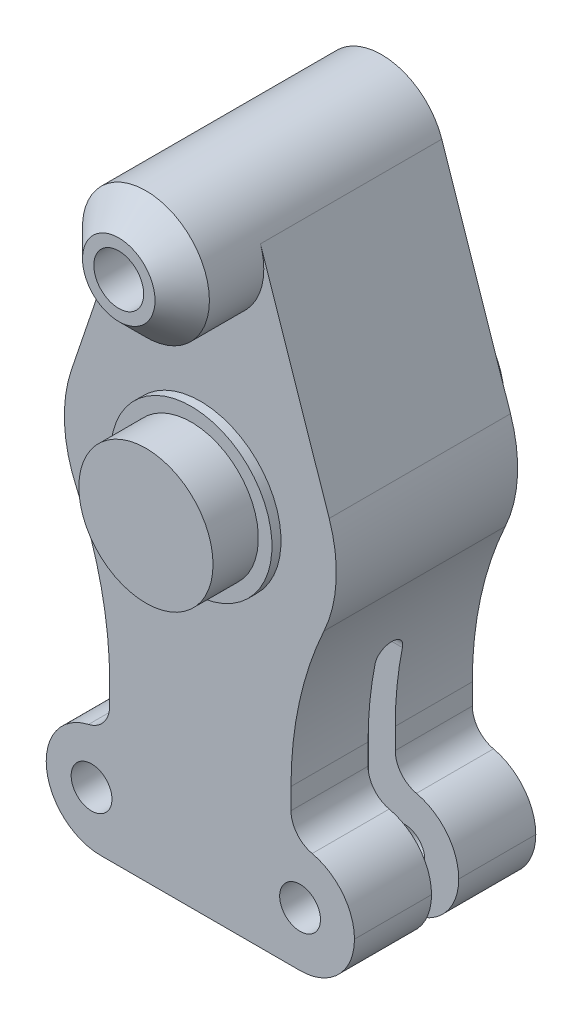
SolidWorks part; units mm, degrees
ref_plane "Спереди" through (0, 0, 0) normal (0, 0, 1) x (1, 0, 0)
ref_plane "Сверху" through (0, 0, 0) normal (0, 1, 0) x (1, 0, 0)
ref_plane "Справа" through (0, 0, 0) normal (1, 0, 0) x (0, 0, -1)
sketch "Эскиз1" plane through (0, 0, 0) normal (0, 0, 1) x (1, 0, 0)
  circle A0 centre (0, 0) radius 7.5 construction
  circle A1 centre (0, 0) radius 7.4
  dimension "D1" = 15
  dimension "measurement_tolerance" = 0.1
extrude "Бобышка-Вытянуть1" add sketch "Эскиз1" along normal blind 5
sketch "Эскиз2" plane through (0, 0, 0) normal (0, 0, -1) x (-1, 0, 0)
  circle A2 centre (0, 0) radius 8.9
  circle A3 centre (0, 0) radius 8.9
  dimension "D1" = 1.5
extrude "Бобышка-Вытянуть2" add sketch "Эскиз2" along normal blind 1
sketch "Эскиз3" plane through (0, 0, -1) normal (0, 0, -1) x (-1, 0, 0)
  circle A0 centre (0, 0) radius 15
  dimension "D3" = 30
extrude "Бобышка-Вытянуть3" add sketch "Эскиз3" along normal blind 20
sketch "Эскиз11" plane through (0, 0, 0) normal (0, 1, 0) x (1, 0, 0)
  line L1 (-10, 1) -> (10, 1)
  line L2 (0, 21) -> (0, 1) construction
  line L3 (15, 21) -> (-15, 21) construction
  line L4 (-8.9, 1) -> (8.9, 1) construction
  line L5 (-10, 1) -> (-10, 21)
  line L6 (-10, 21) -> (10, 21)
  line L7 (10, 1) -> (10, 21)
  line L8 (-10, 1) -> (10, 21) construction
  line L9 (-10, 21) -> (10, 1) construction
  point P0 (0, 11)
  dimension "D2" = 20
extrude "Бобышка-Вытянуть8" add sketch "Эскиз11" against normal blind 40
sketch "Эскиз4" plane through (0, 0, -1) normal (0, 0, -1) x (-1, 0, 0)
  line L0 (0, 0) -> (0, 25) construction
  line L1 (-6.6319, 27.24) -> (-14.2113, 4.8)
  line L2 (-14.2113, 4.8) -> (14.2113, 4.8)
  line L4 (14.2113, 4.8) -> (6.6319, 27.24)
  arc A0 (6.6319, 27.24) -> (-6.6319, 27.24) centre (0, 25) ccw
  circle A1 centre (0, 0) radius 15 construction
  dimension "D1" = 14
  dimension "D2" = 25
extrude "Бобышка-Вытянуть4" add sketch "Эскиз4" along normal up to surface (20 mm away)
sketch "Эскиз5" plane through (0, 0, -1) normal (0, 0, 1) x (1, 0, 0)
  circle A0 centre (0, 25) radius 7
  arc A1 (6.6319, 27.24) -> (-6.6319, 27.24) centre (0, 25) ccw construction
  dimension "D1" = 14
extrude "Бобышка-Вытянуть5" add sketch "Эскиз5" along normal blind 9
hole_wizard "Цековка для винта с внутренним шестигранником M51" positions "Эскиз7" profile "Эскиз6" counterbore size "M5" standard "Ansi Metric" end condition through all
sketch "Эскиз7" plane through (0.4817, 0.6241, -21) normal (0, 0, -1) x (-1, 0, 0)
  circle A0 centre (0.4817, 24.3759) radius 7 construction
  point P1 (0.4817, 24.3759)
sketch "Эскиз6" plane through (0, 25, -21) normal (1, 0, 0) x (0, 1, 0)
  line L0 (0, 0) -> (0, 29)
  line L1 (0, 29) -> (2.75, 29)
  line L3 (2.75, 29) -> (2.75, 14)
  line L4 (2.75, 14) -> (5.25, 14)
  line L5 (5.25, 14) -> (5.25, 0)
  line L7 (5.25, 0) -> (0, 0)
  line L11 (0, -6.35) -> (0, 107.95) construction
  dimension "Диаметр сквозного отверстия" = 5.5
  dimension "Глубина сквозного отверстия" = 29
  dimension "Диаметр цековки" = 10.5
chamfer "Фаска1" distance 3 angle 45 1 edges at (7, 25, 8)
fillet "Скругление20" radius 40 2 edges at (-10, -11.1803, -11) (10, -11.1803, -11)
sketch "Эскиз8" plane through (0, 0, -21) normal (0, 0, -1) x (-1, 0, 0)
  circle A1 centre (0, 0) radius 9
  circle A2 centre (0, 0) radius 7.5 construction
  dimension "D1" = 15
  dimension "D2" = 1.5
extrude "Бобышка-Вытянуть6" add sketch "Эскиз8" along normal blind 1
sketch "Эскиз9" plane through (0, 0, -22) normal (0, 0, -1) x (-1, 0, 0)
  circle A2 centre (0, 0) radius 7.5 construction
  circle A3 centre (0, 0) radius 7.5
  circle A4 centre (0, 0) radius 7.6 construction
  dimension "measurement_tolerance" = 0.1
extrude "Бобышка-Вытянуть7" add sketch "Эскиз9" along normal blind 5
sketch "Эскиз10" plane through (0, 0, 5) normal (0, 0, 1) x (1, 0, 0)
  circle A0 centre (0, 0) radius 3.25
  dimension "D1" = 6.5
extrude "Вырез-Вытянуть1" [suppressed] cut sketch "Эскиз10" against normal through all
sketch "Эскиз13" plane through (0, -40, 0) normal (0, -1, 0) x (-1, 0, 0)
  line L0 (10, 11) -> (-10, 11) construction
  line L1 (-10, 1) -> (-10, 21) construction
  line L2 (-17, 1) -> (17, 1)
  line L3 (-17, 1) -> (-17, 21)
  line L4 (-17, 21) -> (17, 21)
  line L5 (17, 1) -> (17, 21)
  line L6 (-17, 1) -> (17, 21) construction
  line L7 (-17, 21) -> (17, 1) construction
  line L8 (10, 21) -> (10, 1) construction
  point P0 (0, 11)
  dimension "D1" = 20
  dimension "D2" = 34
extrude "Бобышка-Вытянуть9" add sketch "Эскиз13" against normal blind 12
sketch "Эскиз14" plane through (0, -40, 0) normal (0, -1, 0) x (-1, 0, 0)
  line L0 (0, 1) -> (0, 11) construction
  line L1 (-17, 1) -> (17, 1) construction
  line L2 (0, 11) -> (17, 11) construction
  line L3 (17, 1) -> (17, 21) construction
  circle A0 centre (0, 11) radius 7.2
  dimension "D1" = 14.4
extrude "Вырез-Вытянуть3" cut sketch "Эскиз14" against normal blind 45
sketch "Эскиз15" plane through (0, -40, 0) normal (0, -1, 0) x (-1, 0, 0)
  line L0 (-17, 11) -> (17, 11) construction
  line L1 (-17, 12.5) -> (17, 12.5)
  line L2 (-17, 12.5) -> (-17, 9.5)
  line L3 (-17, 9.5) -> (17, 9.5)
  line L4 (17, 12.5) -> (17, 9.5)
  line L5 (-17, 21) -> (-17, 1) construction
  line L6 (17, 1) -> (17, 21) construction
  point P8 (0, 11)
  dimension "D1" = 3
extrude "Вырез-Вытянуть4" cut sketch "Эскиз15" against normal blind 25
sketch "Эскиз16" plane through (0, 0, 0) normal (1, 0, 0) x (0, 0, -1)
  line L0 (9.5, -15) -> (12.5, -15)
  line L1 (9.5, -15) -> (12.5, -15) construction
  arc A0 (12.5, -15) -> (9.5, -15) centre (11, -15) ccw
extrude "Вырез-Вытянуть5" cut sketch "Эскиз16" against normal through all and the other way through all
fillet "Скругление12" [suppressed] radius 3
fillet "Скругление14" radius 1 2 edges at (0, -40, -3.8) (0, -40, -18.2)
sketch "Эскиз17" plane through (0, 0, -21) normal (0, 0, -1) x (-1, 0, 0)
  line L0 (0, 25) -> (0, 15) construction
  line L1 (5.25, 25) -> (5.25, 15)
  line L2 (-5.25, 25) -> (-5.25, 15)
  circle A1 centre (0, 25) radius 5.25 construction
  arc A2 (5.25, 25) -> (-5.25, 25) centre (0, 25) ccw
  arc A3 (-5.25, 15) -> (5.25, 15) centre (0, 15) ccw
  point P5 (0, 20)
  dimension "D1" = 10
extrude "Вырез-Вытянуть6" cut sketch "Эскиз17" against normal offset from surface (14 mm away) 15 up to face at (4, 25, 8)
ref_plane "Плоскость1" through (0, 15, 0) normal (0, -1, 0) x (-1, 0, 0)
sketch "Эскиз18" plane through (0, 15, 0) normal (0, -1, 0) x (-1, 0, 0)
  line L0 (-5.25, 7) -> (5.25, 7)
  line L1 (5.25, 7) -> (5.25, 15.9272)
  line L2 (-5.25, 7) -> (-5.25, 15.9272)
  arc A0 (-5.25, 15.9272) -> (5.25, 15.9272) centre (0, 11) cw
  arc A2 (-7.042, 12.5) -> (7.042, 12.5) centre (0, 11) ccw construction
extrude "Вырез-Вытянуть7" cut sketch "Эскиз18" along normal through all
sketch "Эскиз19" plane through (0, 0, -27) normal (0, 0, -1) x (-1, 0, 0)
  line L1 (-2.7, -5.2) -> (2.7, -5.2)
  line L2 (-2.7, -5.2) -> (-2.7, 5.2)
  line L3 (-2.7, 5.2) -> (2.7, 5.2)
  line L4 (2.7, -5.2) -> (2.7, 5.2)
  line L5 (-2.7, -5.2) -> (2.7, 5.2) construction
  line L6 (-2.7, 5.2) -> (2.7, -5.2) construction
  point P0 (0, 0)
  dimension "D1" = 5.4
  dimension "D2" = 10.4
extrude "Вырез-Вытянуть8" cut sketch "Эскиз19" against normal blind 5
fillet "Скругление15" radius 1 3 edges at (5.25, 15, -7) (0, 30.25, -7) (-5.25, 15, -7)
fillet "Скругление18" radius 0.4 4 edges at (2.7, 5.2, -24.5) (-2.7, 5.2, -24.5) (2.7, -5.2, -24.5) (-2.7, -5.2, -24.5)
hole_wizard "Отверстие с зазором M41" positions "Эскиз21" profile "Эскиз20" hole size "M4" standard "Ansi Metric" end condition through all
sketch "Эскиз21" plane through (0, 0, -1) normal (0, 0, 1) x (1, 0, 0)
  line L0 (17, -34) -> (-17, -34) construction
  line L1 (17, -28) -> (17, -40) construction
  line L2 (-17, -28) -> (-17, -40) construction
  point P0 (-12, -34)
  point P2 (11, -34)
  dimension "D1" = 6
  dimension "D2" = 5
sketch "Эскиз20" plane through (-12, -34, -1) normal (1, 0, 0) x (0, -1, 0)
  line L0 (0, 0) -> (0, 26)
  line L1 (0, 26) -> (2.25, 26)
  line L2 (2.25, 26) -> (2.25, 0)
  line L5 (2.25, 0) -> (0, 0)
  line L11 (0, -6.35) -> (0, 107.95) construction
  dimension "Диаметр сквозного отверстия" = 4.5
  dimension "Глубина сквозного отверстия" = 26
fillet "Скругление19" radius 6 8 edges at (17, -28, -16.75) (17, -28, -5.25) (17, -40, -5.25) (17, -40, -16.75) (-17, -40, -16.75) (-17, -28, -16.75) (-17, -28, -5.25) (-17, -40, -5.25)
fillet "Скругление21" radius 3 4 edges at (10, -28, -16.75) (10, -28, -5.25) (-10, -28, -16.75) (-10, -28, -5.25)
